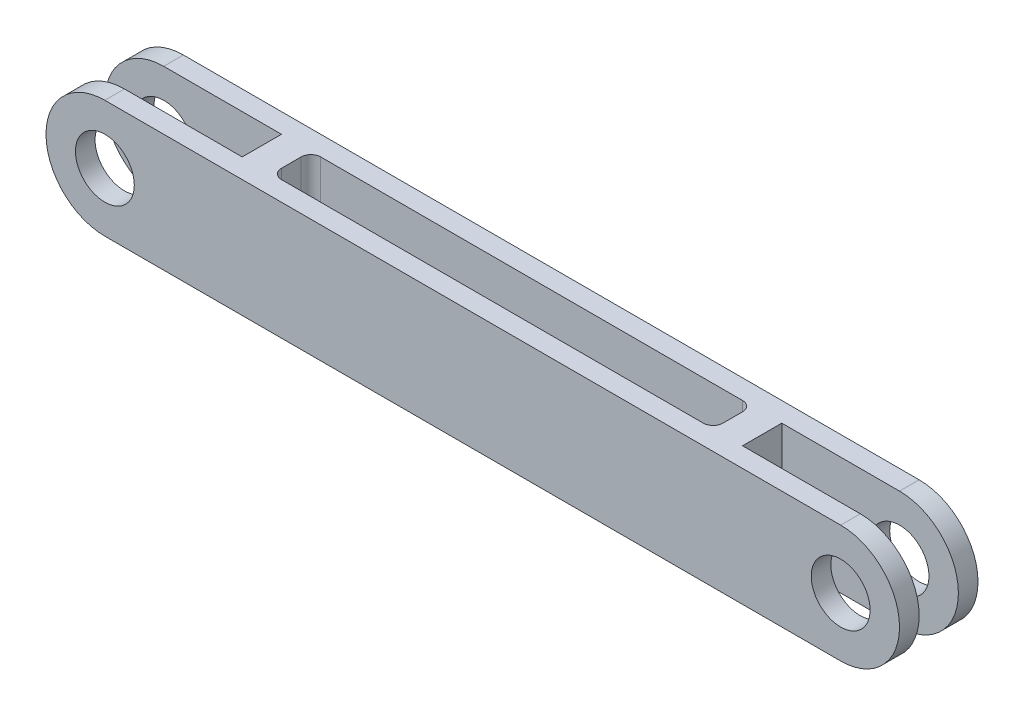
SolidWorks part; units mm, degrees
ref_plane "前视基准面" through (0, 0, 0) normal (0, 0, 1) x (1, 0, 0)
ref_plane "上视基准面" through (0, 0, 0) normal (0, 1, 0) x (1, 0, 0)
ref_plane "右视基准面" through (0, 0, 0) normal (1, 0, 0) x (0, 0, -1)
sketch "草图1" plane through (0, 0, 0) normal (0, 0, 1) x (1, 0, 0)
  line L0 (-37.5, 0) -> (37.5, 0) construction
  line L1 (-37.5, 6) -> (37.5, 6)
  line L2 (-37.5, -6) -> (37.5, -6)
  arc A0 (-37.5, 6) -> (-37.5, -6) centre (-37.5, 0) ccw
  arc A1 (37.5, -6) -> (37.5, 6) centre (37.5, 0) ccw
  circle A2 centre (-37.5, 0) radius 3
  circle A3 centre (37.5, 0) radius 3
  point P3 (0, 0)
  dimension "D3" = 6
  dimension "D4" = 6
  dimension "D1" = 12
  dimension "D2" = 75
extrude "凸台-拉伸1" add sketch "草图1" along normal blind 8
sketch "草图2" plane through (0, 6, 0) normal (0, 1, 0) x (1, 0, 0)
  line L0 (-37.5, 0) -> (-43.5, 0) construction
  line L1 (-43.5, -2) -> (-25.5, -2)
  line L2 (-43.5, -2) -> (-43.5, -6)
  line L3 (-43.5, -6) -> (-25.5, -6)
  line L4 (-25.5, -2) -> (-25.5, -6)
  line L5 (-37.5, -8) -> (-37.5, 0) construction
  line L6 (0, 0) -> (0, -21.7228) construction
  line L7 (37.5, 0) -> (-37.5, 0) construction
  line L8 (25.5, -2) -> (25.5, -6)
  line L9 (43.5, -6) -> (25.5, -6)
  line L10 (43.5, -2) -> (43.5, -6)
  line L11 (43.5, -2) -> (25.5, -2)
  line L13 (-21.5, -6) -> (21.5, -6)
  line L14 (-22.5, -5) -> (-22.5, -3)
  line L15 (-21.5, -2) -> (21.5, -2)
  line L16 (22.5, -5) -> (22.5, -3)
  line L17 (-22.5, -6) -> (22.5, -2) construction
  line L18 (-22.5, -2) -> (22.5, -6) construction
  arc A0 (-21.5, -6) -> (-22.5, -5) centre (-21.5, -5) cw
  arc A1 (-22.5, -3) -> (-21.5, -2) centre (-21.5, -3) cw
  arc A2 (21.5, -6) -> (22.5, -5) centre (21.5, -5) ccw
  arc A3 (21.5, -2) -> (22.5, -3) centre (21.5, -3) cw
  point P16 (0, -4)
  dimension "D7" = 1
  dimension "D1" = 4
  dimension "D2" = 2
  dimension "D3" = 6
  dimension "D4" = 18
  dimension "D5" = 4
  dimension "D6" = 45
extrude "切除-拉伸1" cut sketch "草图2" against normal through all
